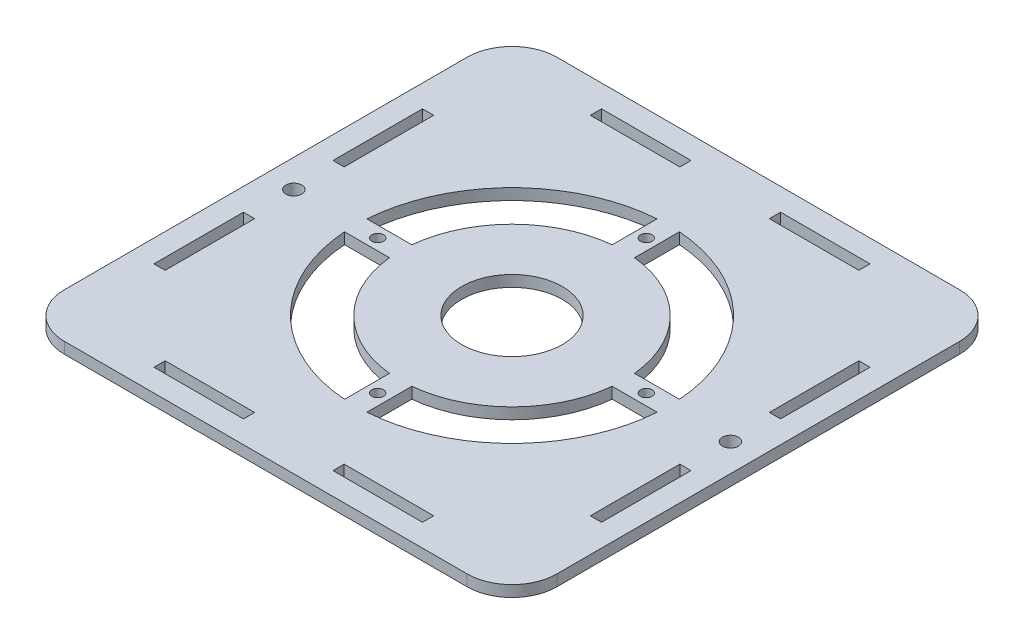
SolidWorks part; units mm, degrees
ref_plane "Front Plane" through (0, 0, 0) normal (0, 0, 1) x (1, 0, 0)
ref_plane "Top Plane" through (0, 0, 0) normal (0, 1, 0) x (1, 0, 0)
ref_plane "Right Plane" through (0, 0, 0) normal (1, 0, 0) x (0, 0, -1)
sketch "Sketch1" plane through (0, 0, 0) normal (0, 1, 0) x (1, 0, 0)
  line L1 (0, 0) -> (139.7, 0)
  line L2 (0, 0) -> (0, 139.7)
  line L3 (0, 139.7) -> (139.7, 139.7)
  line L4 (139.7, 0) -> (139.7, 139.7)
  dimension "D1" = 139.7
  dimension "D2" = 139.7
extrude "Boss-Extrude1" add sketch "Sketch1" along normal blind 3.175
sketch "Sketch13" plane through (0, 3.175, 0) normal (0, 1, 0) x (1, 0, 0)
  line L1 (0, 139.7) -> (0, 0) construction
  line L2 (31.75, 9.525) -> (57.15, 9.525)
  line L3 (31.75, 9.525) -> (31.75, 6.35)
  line L4 (31.75, 6.35) -> (57.15, 6.35)
  line L5 (57.15, 9.525) -> (57.15, 6.35)
  line L6 (31.75, 9.525) -> (57.15, 6.35) construction
  line L7 (31.75, 6.35) -> (57.15, 9.525) construction
  line L8 (0, 0) -> (139.7, 0) construction
  line L9 (82.55, 9.525) -> (107.95, 9.525)
  line L10 (82.55, 9.525) -> (82.55, 6.35)
  line L11 (82.55, 6.35) -> (107.95, 6.35)
  line L12 (107.95, 9.525) -> (107.95, 6.35)
  point P0 (44.45, 7.9375)
  dimension "D1" = 31.75
  dimension "D2" = 3.175
  dimension "D4" = 6.35
  dimension "D5" = 2
  dimension "D3" = 25.4
extrude "Cut-Extrude6" cut sketch "Sketch13" against normal blind 6.35
pattern_linear "LPattern7" count 2 spacing 123.825 along (0, 0, -1) of "Cut-Extrude6"
sketch "Sketch14" plane through (0, 3.175, 0) normal (0, 1, 0) x (1, 0, 0)
  line L0 (0, 139.7) -> (0, 0) construction
  line L1 (6.35, 31.75) -> (9.525, 31.75)
  line L2 (6.35, 31.75) -> (6.35, 57.15)
  line L3 (6.35, 57.15) -> (9.525, 57.15)
  line L4 (9.525, 31.75) -> (9.525, 57.15)
  line L5 (0, 0) -> (139.7, 0) construction
  line L6 (130.175, 57.15) -> (133.35, 57.15)
  line L7 (130.175, 31.75) -> (130.175, 57.15)
  line L8 (133.35, 31.75) -> (133.35, 57.15)
  line L9 (130.175, 31.75) -> (133.35, 31.75)
  line L10 (130.175, 107.95) -> (133.35, 107.95)
  line L11 (130.175, 82.55) -> (130.175, 107.95)
  line L12 (133.35, 82.55) -> (133.35, 107.95)
  line L13 (130.175, 82.55) -> (133.35, 82.55)
  line L14 (6.35, 107.95) -> (9.525, 107.95)
  line L15 (6.35, 82.55) -> (6.35, 107.95)
  line L16 (9.525, 82.55) -> (9.525, 107.95)
  line L17 (6.35, 82.55) -> (9.525, 82.55)
  dimension "D1" = 25.4
  dimension "D2" = 3.175
  dimension "D3" = 6.35
  dimension "D4" = 31.75
  dimension "D5" = 2
  dimension "D6" = 2
extrude "Cut-Extrude7" cut sketch "Sketch14" against normal blind 6.35
hole_wizard "#8 Clearance Hole1" positions "Sketch16" profile "Sketch15" hole size "#8" standard "ANSI Inch"
sketch "Sketch16" plane through (0, 3.175, 0) normal (0, 1, 0) x (1, 0, 0)
  line L0 (9.525, 57.15) -> (6.35, 57.15) construction
  line L1 (6.35, 57.15) -> (6.35, 31.75) construction
  line L4 (130.175, 107.95) -> (130.175, 82.55) construction
  line L5 (133.35, 57.15) -> (130.175, 57.15) construction
  point P0 (7.9375, 69.85)
  point P3 (7.9375, 57.15)
  point P8 (131.826, 69.85)
  point P18 (131.7625, 57.15)
  dimension "D1" = 12.7
  dimension "D2" = 1.5875
  dimension "D3" = 1.651
  dimension "D4" = 12.7
sketch "Sketch15" plane through (7.9375, 3.175, -69.85) normal (1, 0, 0) x (0, 0, 1)
  line L0 (0, 0) -> (0, 11.5107)
  line L1 (0, 11.5107) -> (2.2479, 10.16)
  line L2 (2.2479, 10.16) -> (2.2479, 0)
  line L5 (2.2479, 0) -> (0, 0)
  line L10 (0, 11.5107) -> (-2.2479, 10.16) construction
  line L11 (0, -6.35) -> (0, 107.95) construction
  dimension "Hole Dia." = 4.4958
  dimension "Hole Depth" = 10.16
  dimension "Drill Angle" = 118
sketch "Sketch18" plane through (0, 3.175, 0) normal (0, 1, 0) x (1, 0, 0)
  line L0 (0, 139.7) -> (0, 0) construction
  circle A0 centre (69.85, 69.85) radius 14.2875
  circle A2 centre (7.9375, 69.85) radius 2.2479 construction
  dimension "D1" = 28.575
  dimension "D2" = 69.85
  dimension "D3" = 0
extrude "Cut-Extrude9" cut sketch "Sketch18" against normal blind 7.62
sketch "Sketch19" plane through (0, 3.175, 0) normal (0, 1, 0) x (1, 0, 0)
  line L0 (12.7, 82.55) -> (177.8, 82.55)
  line L3 (9.525, 107.95) -> (6.35, 107.95) construction
  dimension "D1" = 25.4
sketch "Sketch20" plane through (0, 3.175, 0) normal (0, 1, 0) x (1, 0, 0)
  text T0 "Countercat" font "DS-Digital" height in points 72
extrude "Cut-Extrude10" [suppressed] cut sketch "Sketch20" against normal blind 10.16
sketch "Sketch21" plane through (0, 3.175, 0) normal (0, 1, 0) x (1, 0, 0)
  line L0 (12.7, 69.85) -> (63.5, 69.85)
  line L2 (177.8, 69.85) -> (127, 69.85)
  circle A0 centre (69.85, 69.85) radius 14.2875 construction
  dimension "D1" = 50.8
  dimension "D2" = 50.8
  dimension "D3" = 0
  dimension "D4" = 0
sketch "Sketch22" plane through (0, 3.175, 0) normal (0, 1, 0) x (1, 0, 0)
  text T0 "armed" font "DS-Digital" height in points 36
  text T1 "Safe" font "DS-Digital" height in points 36
extrude "Cut-Extrude11" [suppressed] cut sketch "Sketch22" against normal blind 10.16
sketch "Sketch24" plane through (0, 3.175, 0) normal (0, 1, 0) x (1, 0, 0)
  line L0 (6.35, 82.55) -> (9.525, 82.55) construction
  line L2 (33.3375, 87.63) -> (33.3375, 69.85)
  line L4 (40.7602, 81.4016) -> (33.3375, 87.63)
  line L7 (60.325, 87.63) -> (58.7375, 69.85)
  line L8 (52.5256, 80.7677) -> (60.325, 87.63)
  arc A0 (52.5256, 80.7677) -> (40.7602, 81.4016) centre (46.0375, 69.85) ccw
  arc A1 (33.3375, 69.85) -> (58.7375, 69.85) centre (46.0375, 69.85) ccw
  circle A2 centre (7.9375, 69.85) radius 2.2479 construction
  arc A7 (40.7602, 81.4016) -> (39.5537, 80.7702) centre (46.0375, 69.85) ccw
  arc A8 (33.3375, 69.85) -> (34.5363, 75.2364) centre (46.0375, 69.85) cw
  arc A9 (52.5256, 80.7677) -> (54.5658, 79.2605) centre (46.0375, 69.85) cw
  arc A10 (58.7375, 69.85) -> (57.9981, 74.1202) centre (46.0375, 69.85) ccw
  point P1 (7.9375, 82.55)
  dimension "D1" = 25.4
  dimension "D2" = 12.7
  dimension "D3" = 38.1
  dimension "D4" = 50
extrude "Cut-Extrude16" [suppressed] cut sketch "Sketch24" against normal blind 6.35
fillet "Fillet2" [suppressed] radius 0.508
fillet "Fillet6" radius 12.7 4 edges at (139.7, 1.5875, -139.7) (139.7, 1.5875, 0) (0, 1.5875, 0) (0, 1.5875, -139.7)
sketch "Sketch26" plane through (0, 3.175, 0) normal (0, 1, 0) x (1, 0, 0)
  line L1 (66.675, 25.4) -> (73.025, 25.4)
  line L2 (66.675, 25.4) -> (66.675, 114.3)
  line L3 (66.675, 114.3) -> (73.025, 114.3)
  line L4 (73.025, 25.4) -> (73.025, 114.3)
  line L5 (66.675, 25.4) -> (73.025, 114.3) construction
  line L6 (66.675, 114.3) -> (73.025, 25.4) construction
  line L7 (25.5135, 73.025) -> (114.1865, 73.025)
  line L8 (25.5135, 73.025) -> (25.5135, 66.675)
  line L9 (25.5135, 66.675) -> (114.1865, 66.675)
  line L10 (114.1865, 73.025) -> (114.1865, 66.675)
  line L11 (25.5135, 73.025) -> (114.1865, 66.675) construction
  line L12 (25.5135, 66.675) -> (114.1865, 73.025) construction
  circle A0 centre (69.85, 69.85) radius 44.45
  circle A1 centre (69.85, 69.85) radius 31.75
  point P0 (69.85, 69.85)
  dimension "D3" = 63.5
  dimension "D1" = 6.35
  dimension "D2" = 88.9
  dimension "D4" = 6.35
extrude "Cut-Extrude17" cut sketch "Sketch26" against normal blind 7.62 contours A1 L2 A0 L7 | A1 L9 A0 L2 | A1 L4 A0 L9 | A1 L7 A0 L4 region at (44.8165, 3.175, -44.8165) region at (94.8835, 3.175, -44.8165) region at (44.8165, 3.175, -94.8835) region at (94.8835, 3.175, -94.8835)
hole_wizard "#4 Clearance Hole1" positions "Sketch28" profile "Sketch27" hole size "#4" standard "ANSI Inch"
sketch "Sketch28" plane through (0, 3.175, 0) normal (0, 1, 0) x (1, 0, 0)
  circle A0 centre (69.85, 69.85) radius 14.2875 construction
  point P0 (69.85, 107.95)
  dimension "D1" = 38.1
sketch "Sketch27" plane through (69.85, 3.175, -107.95) normal (1, 0, 0) x (0, 0, 1)
  line L0 (0, 0) -> (0, 11.1406)
  line L1 (0, 11.1406) -> (1.6319, 10.16)
  line L2 (1.6319, 10.16) -> (1.6319, 0)
  line L5 (1.6319, 0) -> (0, 0)
  line L10 (0, 11.1406) -> (-1.6319, 10.16) construction
  line L11 (0, -6.35) -> (0, 107.95) construction
  dimension "Hole Dia." = 3.2639
  dimension "Hole Depth" = 10.16
  dimension "Drill Angle" = 118
pattern_circular "CirPattern1" count 4 every 90 about axis through (69.85, 3.175, -69.85) along (0, 1, 0) of "#4 Clearance Hole1"
equation "\"THICK\"= .25"
